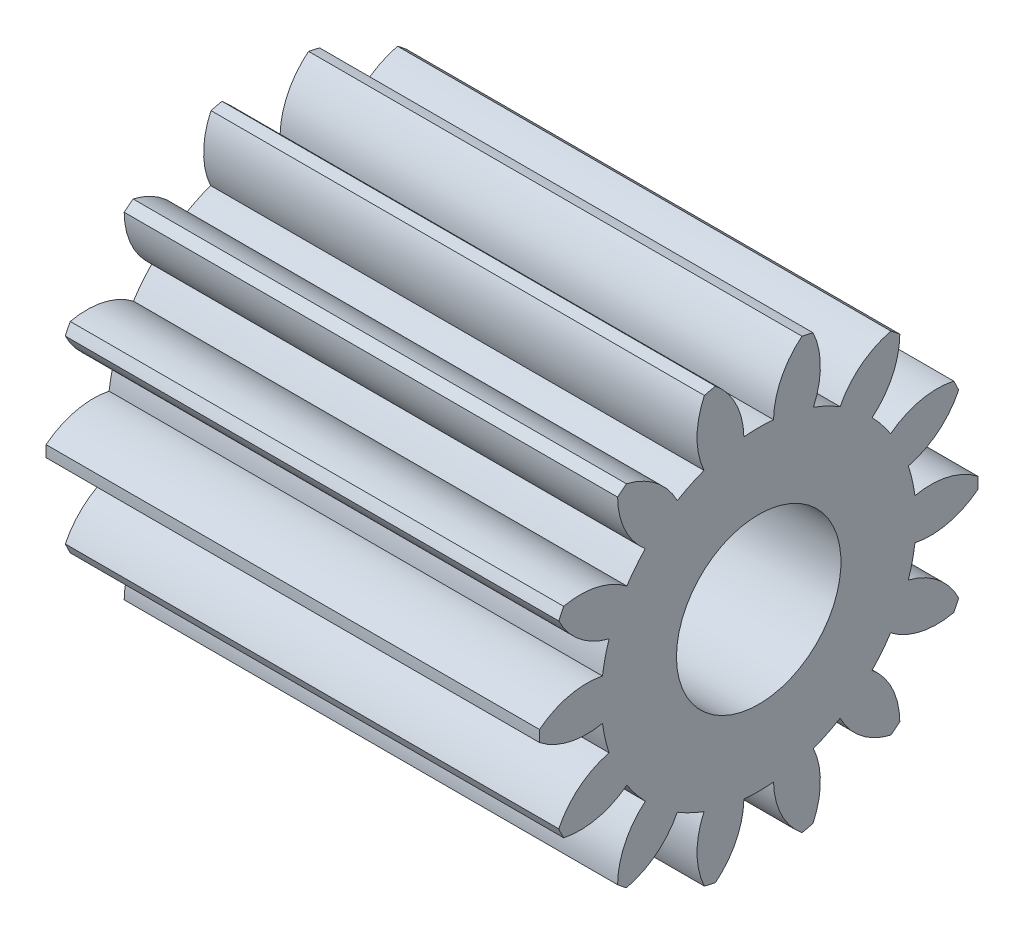
SolidWorks part; units mm, degrees
ref_plane "Plane1" through (0, 0, 0) normal (0, 0, 1) x (1, 0, 0)
ref_plane "Plane2" through (0, 0, 0) normal (0, 1, 0) x (1, 0, 0)
ref_plane "Plane3" through (0, 0, 0) normal (1, 0, 0) x (0, 0, -1)
sketch "HoldingSke" plane through (0, 0, 0) normal (0, 1, 0) x (1, 0, 0)
  line L0 (0, 0) -> (1.9406, -0.4838)
  line L1 (-15, 0) -> (100, 0) construction
  line L2 (0, 0) -> (-2.1039, 2.3779)
  line L3 (0, 0) -> (-11.863, 4.5341)
  line L4 (0, 0) -> (8.3795, 2.0892)
  line L5 (0, 0) -> (-46.8476, -17.4728)
  line L6 (0, 0) -> (-7.4607, -5.0337)
  line L7 (-2.1039, 2.3779) -> (8.6586, 51.2059)
  line L8 (-76.2, 54.61) -> (-75.7, 54.61)
  line L9 (-71.009, 38.7566) -> (-53.1078, 45.2721)
  line L10 (-76.2, 71.12) -> (104.1128, 71.12)
  line L11 (0, 0) -> (-9, 0)
  line L12 (-76.2, 101.6) -> (-76.181, 101.6)
  line L13 (24.9733, 27.94) -> (52.9518, 28.4284)
  line L14 (24.9733, 27.94) -> (24.9743, 27.94)
  line L15 (24.9733, 27.94) -> (100.4006, 29.5858)
  line L16 (-63.627, -0.5) -> (-12.827, -0.5)
  circle A0 centre (0, 0) radius 1.5
  circle A1 centre (0, 0) radius 2.874
  circle A2 centre (0, 0) radius 37.5
  circle A3 centre (0, 0) radius 1.5
  dimension "Num_teeth" = 14
  dimension "Pitch_radius" = 180.3128
  dimension "Width" = 9
  dimension "Thickness" = 9
sketch "BasProSke" plane through (0, 0, 0) normal (0, 1, 0) x (1, 0, 0)
  line L0 (-10, 0) -> (60, 0) construction
  line L1 (0, 0) -> (0, 4)
  line L2 (0, 0) -> (9, 0)
  line L3 (9, 0) -> (9, 4)
  line L4 (9, 4) -> (0, 4)
  dimension "Thickness" = 9
  dimension "Diameter" = 8
revolve "Base-Revolve" add sketch "BasProSke" angle 360 about L0
sketch "TooCutSke" plane through (0, 0, 0) normal (1, 0, 0) x (0, 0, -1)
  line L1 (0, 0) -> (0, 107) construction
  line L2 (0, 0) -> (-0.4251, 3.4741) construction
  line L3 (0, 0) -> (-1.5494, 6.7886) construction
  line L4 (-0.4251, 3.4741) -> (-0.7747, 3.3943) construction
  arc A0 (0.2702, 2.8613) -> (-0.2702, 2.8613) centre (0, 0) ccw
  arc A1 (0.8149, 3.942) -> (-0.8149, 3.942) centre (0, 0) ccw
  circle A2 centre (0, 0) radius 3.5 construction
  circle A3 centre (0, 0) radius 3.2889 construction
  arc A4 (-0.2702, 2.8613) -> (-0.8149, 3.942) centre (-1.6699, 2.8334) ccw
  arc A5 (0.8149, 3.942) -> (0.2702, 2.8613) centre (1.6699, 2.8334) ccw
extrude "ToothCut" cut sketch "TooCutSke" along normal through all
fillet "Breaks" [suppressed] radius 0.01 tangent propagation no
fillet "RootFillets" [suppressed] radius 0.126
pattern_circular "TeethCuts" count 14 every 25.714 about axis through (-10, 0, 0) along (1, 0, 0) of "ToothCut", "RootFillets", "Breaks"
sketch "HubNeaOneSke" plane through (0, 0, 0) normal (-1, 0, 0) x (0, 0, 1)
  circle A0 centre (0, 0) radius 2.874
  dimension "Diameter" = 5.748
extrude "HubNearOne" [suppressed] add sketch "HubNeaOneSke" along normal blind 41.0001
sketch "HubNeaBotSke" plane through (0, 0, 0) normal (-1, 0, 0) x (0, 0, 1)
  circle A0 centre (0, 0) radius 2.874
  dimension "Diameter" = 5.748
extrude "HubNearBoth" [suppressed] add sketch "HubNeaBotSke" along normal blind 20.5
ref_plane "FarPln" through (9, 0, 0) normal (1, 0, 0) x (0, 0, -1)
sketch "HubFarSke" plane through (9, 0, 0) normal (1, 0, 0) x (0, 0, -1)
  circle A0 centre (0, 0) radius 2.874
  dimension "Diameter" = 5.748
extrude "HubFar" [suppressed] add sketch "HubFarSke" along normal blind 20.5
sketch "BorSke" plane through (0, 0, 0) normal (1, 0, 0) x (0, 0, -1)
  circle A0 centre (0, 0) radius 1.5
  dimension "Diameter" = 3
extrude "Bore" cut sketch "BorSke" along normal mid plane 100.0001
sketch "KeySke" plane through (0, 0, 0) normal (1, 0, 0) x (0, 0, -1)
  line L0 (-0.6, 0) -> (-0.6, 2)
  line L1 (-0.6, 2) -> (0.6, 2)
  line L2 (0.6, 2) -> (0.6, 0)
  line L3 (0, 0) -> (0, 34) construction
  line L4 (-0.6, 0) -> (0.6, 0)
  dimension "Width" = 1.2
extrude "Keyway" [suppressed] cut sketch "KeySke" along normal mid plane 100.0001
pattern_circular "Keyway2" [suppressed] count 2 every 90 about axis through (-10, 0, 0) along (1, 0, 0) reverse direction yes
equation "' \"Module@HoldingSke\" = 6.35"
equation "' \"Num_teeth@HoldingSke\" = 12"
equation "' \"Ap@HoldingSke\" =  20"
equation "' \"Ap@HoldingSke\" = 20"
equation "' \"Width@HoldingSke\" = 0.5 * 25.4"
equation "' \"Hub_dia@HoldingSke\"= 1 * 25.4"
equation "' \"Hub_dia@HoldingSke\" = 1 * 25.4"
equation "' \"Overall_len@HoldingSke\" = 1.0 * 25.4"
equation "' \"Bore@HoldingSke\" = 0.75 * 25.4"
equation "' \"T_dim@HoldingSke\" = 0.1 * 25.4"
equation "' \"Width@KeySke\" = 0.25 * 25.4"
equation "' \"Show_teeth@HoldingSke\" = 13"
equation "' \"Backlash@HoldingSke\" = 0.009 * 25.4"
equation "' \"Addendum_fac@HoldingSke\" = 1.0"
equation "' \"Dedendum_fac@HoldingSke\" = 1.25"
equation "' \"Dedendum_add@HoldingSke\" = 0.00005 * 25.4"
equation "' \"Clearance_fac@HoldingSke\" = 0.25"
equation "\"Pitch@HoldingSke\" = 1 / \"Module@HoldingSke\""
equation "\"Overcut_dia@TooCutSke\" = (\"Num_teeth@HoldingSke\" + 2 * \"Addendum_fac@HoldingSke\") / \"Pitch@HoldingSke\" + 0.002 * 25.4"
equation "\"Pitch_dia@TooCutSke\" = \"Num_teeth@HoldingSke\" / \"Pitch@HoldingSke\""
equation "\"Base_dia@TooCutSke\" = \"Num_teeth@HoldingSke\" / \"Pitch@HoldingSke\" * cos((\"Ap@HoldingSke\"  * 3.14159265 / 180))"
equation "\"Root_dia@TooCutSke\" = (\"Num_teeth@HoldingSke\" + 2) / \"Pitch@HoldingSke\" - 2 * (\"Addendum_fac@HoldingSke\" + \"Dedendum_fac@HoldingSke\") / \"Pitch@HoldingSke\" - \"Dedendum_add@HoldingSke\" * 2"
equation "\"Half_ang@TooCutSke\" = 180 / \"Num_teeth@HoldingSke\""
equation "\"Half_CT@TooCutSke\" = \"Num_teeth@HoldingSke\" / \"Pitch@HoldingSke\" * sin((3.14159265 / 2 / \"Num_teeth@HoldingSke\")) / 2 - 7 * \"Backlash@HoldingSke\" / 4"
equation "\"Flank_rad@TooCutSke\" = \"Num_teeth@HoldingSke\" / \"Pitch@HoldingSke\" / 5"
equation "\"Radius@RootFillets\" = \"Clearance_fac@HoldingSke\" / \"Pitch@HoldingSke\" + \"Dedendum_add@HoldingSke\""
equation "\"Break_rad@Breaks\" = 0.02 / \"Pitch@HoldingSke\""
equation "\"Thickness@HoldingSke\" = \"Width@HoldingSke\""
equation "\"OAL@HoldingSke\" = \"Thickness@HoldingSke\""
equation "\"MHD@HoldingSke\" = (\"Num_teeth@HoldingSke\" + 2) / \"Pitch@HoldingSke\" - 2 * (\"Addendum_fac@HoldingSke\" + \"Dedendum_fac@HoldingSke\")  / \"Pitch@HoldingSke\" - \"Dedendum_add@HoldingSke\" * 2"
equation "\"MBD@HoldingSke\" = (\"Num_teeth@HoldingSke\" + 2) / \"Pitch@HoldingSke\" - 2 * (\"Addendum_fac@HoldingSke\" + \"Dedendum_fac@HoldingSke\")  / \"Pitch@HoldingSke\" - \"Dedendum_add@HoldingSke\" * 2 - 0.002 * 25.4"
equation "\"MHD@HoldingSke\" = ((sgn( \"MHD@HoldingSke\" - \"Hub_dia@HoldingSke\" )-1)*( \"MHD@HoldingSke\" - \"Hub_dia@HoldingSke\" ))/-2+ \"Hub_dia@HoldingSke\""
equation "\"MBD@HoldingSke\" = ((sgn( \"MBD@HoldingSke\" - \"Bore@HoldingSke\" )-1)*( \"MBD@HoldingSke\" - \"Bore@HoldingSke\" ))/-2+ \"Bore@HoldingSke\""
equation "\"OAL@HoldingSke\" = ((sgn( \"OAL@HoldingSke\" - \"Overall_len@HoldingSke\" )+1)*( \"OAL@HoldingSke\" - \"Overall_len@HoldingSke\" ))/2 + \"Overall_len@HoldingSke\" + 0.000002 * 25.4"
equation "\"Num_teeth@TeethCuts\" = int( \"Show_teeth@HoldingSke\" ) + 1"
equation "\"Num_teeth@TeethCuts\" = ((sgn( \"Num_teeth@TeethCuts\" - \"Num_teeth@HoldingSke\" )-1)*( \"Num_teeth@TeethCuts\" - \"Num_teeth@HoldingSke\" ))/-2+ \"Num_teeth@HoldingSke\""
equation "\"Num_teeth@TeethCuts\" = ((sgn( \"Num_teeth@TeethCuts\" - 2.0)+1)*( \"Num_teeth@TeethCuts\" - 2.0))/2 +2.0"
equation "\"Angle@TeethCuts\" = 360.0 / \"Num_teeth@HoldingSke\""
equation "\"Diameter@BasProSke\" = (\"Num_teeth@HoldingSke\" + 2 * \"Addendum_fac@HoldingSke\") / \"Pitch@HoldingSke\""
equation "\"Thickness@BasProSke\"  = \"Thickness@HoldingSke\""
equation "' \"Fillet_rad@BasProSke\" =  \"Thickness@HoldingSke\" * 0.05"
equation "' \"Fillet_rad@BasProSke\" = \"Thickness@HoldingSke\" * 0.05"
equation "\"MHD@HoldingSke\" = ((sgn( \"MHD@HoldingSke\" - \"Root_dia@TooCutSke\" )-1)*( \"MHD@HoldingSke\" - \"Root_dia@TooCutSke\" ))/-2+ \"Root_dia@TooCutSke\""
equation "\"Diameter@HubNeaOneSke\" = \"MHD@HoldingSke\""
equation "\"Length@HubNearOne\" = \"OAL@HoldingSke\" - \"Thickness@BasProSke\""
equation "\"Diameter@HubNeaBotSke\" = \"MHD@HoldingSke\""
equation "\"Length@HubNearBoth\" = ( \"OAL@HoldingSke\" - \"Thickness@BasProSke\" ) / 2.0"
equation "\"Thickness@FarPln\" = \"Thickness@BasProSke\""
equation "\"Diameter@HubFarSke\" = \"MHD@HoldingSke\""
equation "\"Length@HubFar\" = ( \"OAL@HoldingSke\" - \"Thickness@BasProSke\" ) / 2.0"
equation "\"Diameter@BorSke\" = \"MBD@HoldingSke\""
equation "\"D1@Bore\" = \"OAL@HoldingSke\" * 2.0"
equation "\"D1@Keyway\" = \"OAL@HoldingSke\" * 2.0"
equation "\"Offset@KeySke\" = \"T_dim@HoldingSke\" + \"MBD@HoldingSke\" / 2.0"
